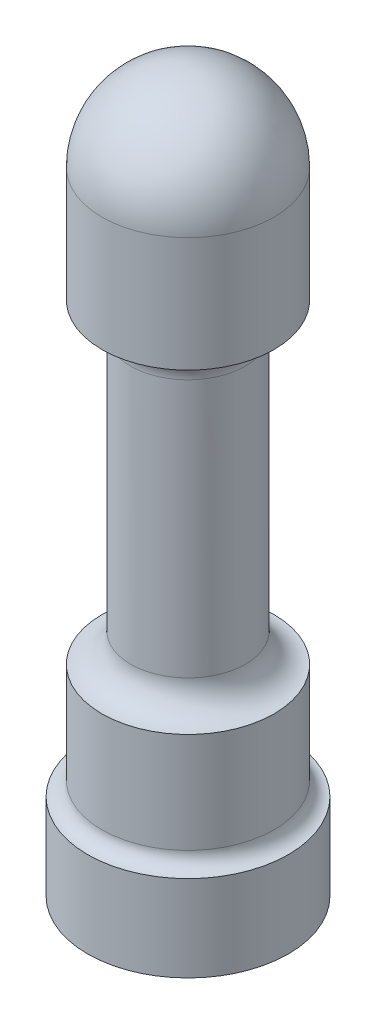
SolidWorks part; units mm, degrees
ref_plane "Front Plane" through (0, 0, 0) normal (0, 0, 1) x (1, 0, 0)
ref_plane "Top Plane" through (0, 0, 0) normal (0, 1, 0) x (1, 0, 0)
ref_plane "Right Plane" through (0, 0, 0) normal (1, 0, 0) x (0, 0, -1)
sketch "Sketch1" plane through (0, 0, 0) normal (0, 0, 1) x (1, 0, 0)
  line L0 (0, 0) -> (3.5, 0)
  line L1 (3.5, 0) -> (3.5, 3)
  line L2 (3.5, 3) -> (3, 3)
  line L3 (3, 3) -> (3, 7)
  line L4 (3, 7) -> (2, 7)
  line L5 (2, 7) -> (2, 18)
  line L6 (2, 18) -> (3, 18)
  line L7 (3, 18) -> (3, 25)
  line L8 (3, 25) -> (0, 25)
  line L9 (0, 25) -> (0, 0)
  point P3 (5.233, 19.9417)
  dimension "D1" = 3.5
  dimension "D2" = 3
  dimension "D3" = 7
  dimension "D4" = 18
  dimension "D5" = 25
  dimension "D6" = 1
  dimension "D7" = 3
  dimension "D8" = 0.5
revolve "Revolve1" add sketch "Sketch1" angle 360 about L9
fillet "Fillet1" radius 3 1 edges at (-3, 25, 0)
fillet "Fillet2" radius 1 2 edges at (-2, 18, 0) (-2, 7, 0)
fillet "Fillet3" radius 0.5 1 edges at (-3, 3, 0)
sketch "Sketch2" plane through (0, 0, 0) normal (0, 0, 1) x (1, 0, 0)
  line L0 (-3.5, 0) -> (3.5, 0) construction
  line L1 (0, 1.5) -> (0, 0)
  line L2 (0, 0) -> (1.5, 0)
  arc A0 (1.5, 0) -> (0, 1.5) centre (0, 0) ccw
  dimension "D1" = 1.5
revolve "Cut-Revolve1" cut sketch "Sketch2" angle 360 about L1
